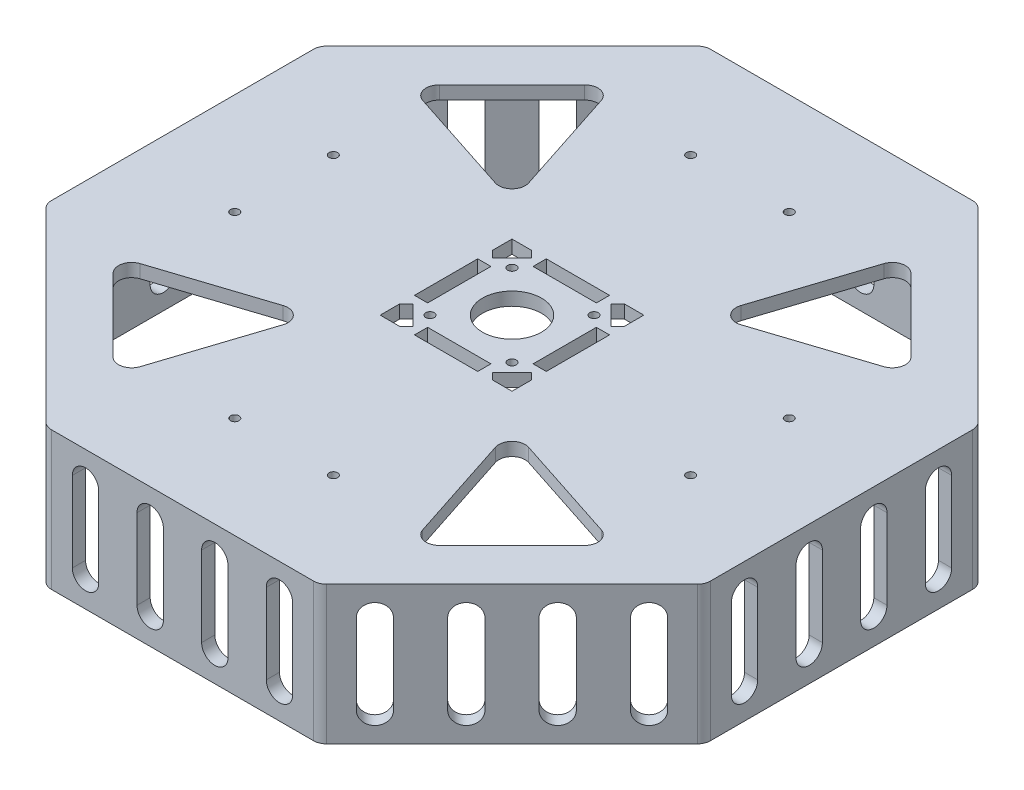
SolidWorks part; units mm, degrees
ref_plane "Front Plane" through (0, 0, 0) normal (0, 0, 1) x (1, 0, 0)
ref_plane "Top Plane" through (0, 0, 0) normal (0, 1, 0) x (1, 0, 0)
ref_plane "Right Plane" through (0, 0, 0) normal (1, 0, 0) x (0, 0, -1)
sketch "Sketch3" plane through (0, 0, 0) normal (0, 1, 0) x (1, 0, 0)
  line L0 (-95.201, 56.1198) -> (-56.1198, 95.201)
  line L7 (-51.7767, 125) -> (-125, 51.7767)
  line L8 (-125, 51.7767) -> (-125, -51.7767)
  line L9 (-125, -51.7767) -> (-51.7767, -125)
  line L10 (-51.7767, -125) -> (51.7767, -125)
  line L11 (51.7767, -125) -> (125, -51.7767)
  line L12 (125, -51.7767) -> (125, 51.7767)
  line L13 (125, 51.7767) -> (51.7767, 125)
  line L14 (51.7767, 125) -> (-51.7767, 125)
  line L15 (-56.1198, 95.201) -> (-37.207, 37.207)
  line L16 (-37.207, 37.207) -> (-95.201, 56.1198)
  line L17 (-47.6346, 115) -> (-115, 47.6346) construction
  line L18 (-115, 47.6346) -> (-115, -47.6346) construction
  line L19 (-115, -47.6346) -> (-47.6346, -115) construction
  line L20 (-47.6346, -115) -> (47.6346, -115) construction
  line L21 (47.6346, -115) -> (115, -47.6346) construction
  line L22 (115, -47.6346) -> (115, 47.6346) construction
  line L23 (115, 47.6346) -> (47.6346, 115) construction
  line L24 (47.6346, 115) -> (-47.6346, 115) construction
  line L25 (-56.1198, 95.201) -> (-61.7767, 100.8579) construction
  line L26 (-95.201, 56.1198) -> (-100.8579, 61.7767) construction
  line L27 (-56.1198, 95.201) -> (-61.7767, 100.8579) construction
  line L28 (-56.1198, 95.201) -> (-41.9777, 109.3431) construction
  line L29 (-61.7767, 100.8579) -> (-47.6346, 115) construction
  line L30 (-41.9777, 109.3431) -> (-47.6346, 115) construction
  line L31 (-95.201, 56.1198) -> (-100.8579, 61.7767) construction
  line L32 (-95.201, 56.1198) -> (-109.3431, 41.9777) construction
  line L33 (-100.8579, 61.7767) -> (-115, 47.6346) construction
  line L34 (-109.3431, 41.9777) -> (-115, 47.6346) construction
  line L35 (37.207, 37.207) -> (56.1198, 95.201)
  line L36 (56.1198, 95.201) -> (95.201, 56.1198)
  line L37 (95.201, 56.1198) -> (37.207, 37.207)
  line L38 (37.207, -37.207) -> (95.201, -56.1198)
  line L39 (95.201, -56.1198) -> (56.1198, -95.201)
  line L40 (56.1198, -95.201) -> (37.207, -37.207)
  line L41 (-37.207, -37.207) -> (-56.1198, -95.201)
  line L42 (-56.1198, -95.201) -> (-95.201, -56.1198)
  line L43 (-95.201, -56.1198) -> (-37.207, -37.207)
  line L44 (-25, -25) -> (-25, 25)
  line L45 (-20, -20) -> (20, -20) construction
  line L46 (-20, -20) -> (-20, 20) construction
  line L47 (-20, 20) -> (20, 20) construction
  line L48 (20, -20) -> (20, 20) construction
  line L49 (-20, -20) -> (20, 20) construction
  line L50 (-20, 20) -> (20, -20) construction
  line L51 (-25, 25) -> (25, 25)
  line L52 (25, -25) -> (25, 25)
  line L53 (-25, -25) -> (25, -25)
  line L54 (-25, 12) -> (-20, 12)
  line L55 (-12, -25) -> (12, -25)
  line L56 (-12, -25) -> (-12, -20)
  line L57 (-12, -20) -> (12, -20)
  line L58 (12, -25) -> (12, -20)
  line L59 (-12, -25) -> (12, -20) construction
  line L60 (-12, -20) -> (12, -25) construction
  line L61 (-25, 12) -> (-25, -12)
  line L62 (-25, -12) -> (-20, -12)
  line L63 (-20, 12) -> (-20, -12)
  line L64 (12, 25) -> (12, 20)
  line L65 (12, 25) -> (-12, 25)
  line L66 (-12, 25) -> (-12, 20)
  line L67 (12, 20) -> (-12, 20)
  line L68 (25, -12) -> (20, -12)
  line L69 (25, -12) -> (25, 12)
  line L70 (25, 12) -> (20, 12)
  line L71 (20, -12) -> (20, 12)
  line L72 (-22.5, 15.1461) -> (-15.1461, 22.5)
  line L73 (-22.5, 15.1461) -> (-25, 17.6461)
  line L74 (-15.1461, 22.5) -> (-17.6461, 25)
  line L75 (-25, 17.6461) -> (-17.6461, 25) construction
  line L76 (-22.5, 15.1461) -> (-17.6461, 25) construction
  line L77 (-15.1461, 22.5) -> (-25, 17.6461) construction
  line L78 (15.1461, 22.5) -> (22.5, 15.1461)
  line L79 (15.1461, 22.5) -> (17.6461, 25)
  line L81 (22.5, 15.1461) -> (25, 17.6461)
  line L82 (22.5, -15.1461) -> (15.1461, -22.5)
  line L83 (22.5, -15.1461) -> (25, -17.6461)
  line L85 (15.1461, -22.5) -> (17.6461, -25)
  line L86 (-15.1461, -22.5) -> (-22.5, -15.1461)
  line L87 (-15.1461, -22.5) -> (-17.6461, -25)
  line L89 (-22.5, -15.1461) -> (-25, -17.6461)
  line L90 (-17.6461, -25) -> (-25, -17.6461) [skipped]
  line L91 (17.6461, 25) -> (25, 17.6461) [skipped]
  line L92 (25, -17.6461) -> (17.6461, -25) [skipped]
  circle A0 centre (0, 0) radius 125 construction
  circle A1 centre (0, 0) radius 11.2
  circle A2 centre (-15.55, 15.55) radius 1.625
  circle A3 centre (15.55, 15.55) radius 1.625
  circle A4 centre (15.55, -15.55) radius 1.625
  circle A5 centre (-15.55, -15.55) radius 1.625
  point P38 (0, 0)
  point P43 (0, -22.5)
  point P52 (0, 0)
  point P53 (0, 20)
  point P54 (-20, 0)
  point P61 (0, -20)
  point P77 (0, 0)
  point P78 (-22.5, 12)
  point P79 (-12, 22.5)
  point P96 (0, 0)
  dimension "D1" = 250
  dimension "D7" = 11.2
  dimension "D8" = 3.25
  dimension "D2" = 10
  dimension "D3" = 20
  dimension "D4" = 8
  dimension "D5" = 61
  dimension "D10" = 31.1
  dimension "D11" = 40
  dimension "D13" = 24
  dimension "D14" = 4
  dimension "D15" = 10.4
  dimension "D16" = 4
  dimension "D12" = 5
  dimension "D6" = 4
  dimension "D9" = 4
extrude "Boss-Extrude3" add sketch "Sketch3" along normal blind 5 contours L13 L14 L7 L8 L9 L10 L11 L12 L53 L44 L51 L52 L15 L16 L0 L36 L37 L35 L39 L40 L38 L42 L43 L41 | L89 L86 L87 L53 L56 L57 L58 L85 L82 L83 L52 L68 L71 L70 L81 L78 L79 L51 L64 L67 L66 L74 L72 L73 L44 L54 L63 L62 A5 A4 A3 A2 A1 region at (0, 0, -121.4645) region at (-24.2929, 0, 14.823)
sketch "Sketch5" plane through (0, 0, 0) normal (0, -1, 0) x (1, 0, 0)
  line L16 (-51.7767, 125) -> (51.7767, 125) construction
  line L17 (51.7767, 125) -> (-51.7767, 125)
  line L18 (-51.7767, 125) -> (-125, 51.7767)
  line L19 (-125, 51.7767) -> (-125, -51.7767)
  line L20 (-125, -51.7767) -> (-51.7767, -125)
  line L21 (-51.7767, -125) -> (51.7767, -125)
  line L22 (51.7767, -125) -> (125, -51.7767)
  line L23 (125, -51.7767) -> (125, 51.7767)
  line L24 (125, 51.7767) -> (51.7767, 125)
  line L25 (125, 51.7767) -> (125, -51.7767) construction
  line L26 (-125, -51.7767) -> (-125, 51.7767) construction
  line L27 (-49.7056, 120) -> (-120, 49.7056)
  line L28 (-120, 49.7056) -> (-120, -49.7056)
  line L29 (-120, -49.7056) -> (-49.7056, -120)
  line L30 (-49.7056, -120) -> (49.7056, -120)
  line L31 (49.7056, -120) -> (120, -49.7056)
  line L32 (120, -49.7056) -> (120, 49.7056)
  line L33 (120, 49.7056) -> (49.7056, 120)
  line L34 (49.7056, 120) -> (-49.7056, 120)
  circle A0 centre (0, 0) radius 125 construction
  dimension "D1" = 5
extrude "Boss-Extrude5" add sketch "Sketch5" along normal blind 47.48
sketch "Sketch6" plane through (-88.3883, 0, 88.3883) normal (-0.7071, 0, 0.7071) x (0.7071, 0, 0.7071)
  line L0 (-51.7767, 5) -> (51.7767, 5) construction
  line L20 (-47.6346, -47.48) -> (51.7767, -47.48)
  line L22 (-47.6346, 5) -> (51.7767, 5)
  line L23 (51.7767, -47.48) -> (51.7767, 5)
  line L29 (-36.7767, -6.04) -> (-36.7767, -36.44) construction
  line L30 (-31.7767, -6.04) -> (-31.7767, -36.44)
  line L35 (-17.2589, -6.04) -> (-17.2589, -36.44)
  line L36 (51.7767, -47.48) -> (-51.7767, -47.48) construction
  line L37 (51.7767, 5) -> (51.7767, -47.48) construction
  line L43 (-41.7767, -6.04) -> (-41.7767, -36.44)
  line L44 (-51.7767, 5) -> (-51.7767, -47.48) construction
  line L45 (-7.2589, -6.04) -> (-7.2589, -36.44)
  line L46 (-12.2589, -6.04) -> (-12.2589, -36.44) construction
  line L47 (7.2589, -6.04) -> (7.2589, -36.44)
  line L48 (17.2589, -6.04) -> (17.2589, -36.44)
  line L49 (12.2589, -6.04) -> (12.2589, -36.44) construction
  line L50 (31.7767, -6.04) -> (31.7767, -36.44)
  line L51 (41.7767, -6.04) -> (41.7767, -36.44)
  line L52 (36.7767, -6.04) -> (36.7767, -36.44) construction
  arc A0 (-31.7767, -6.04) -> (-41.7767, -6.04) centre (-36.7767, -6.04) ccw
  arc A1 (-41.7767, -36.44) -> (-31.7767, -36.44) centre (-36.7767, -36.44) ccw
  arc A2 (-7.2589, -6.04) -> (-17.2589, -6.04) centre (-12.2589, -6.04) ccw
  arc A3 (-17.2589, -36.44) -> (-7.2589, -36.44) centre (-12.2589, -36.44) ccw
  arc A4 (17.2589, -6.04) -> (7.2589, -6.04) centre (12.2589, -6.04) ccw
  arc A5 (7.2589, -36.44) -> (17.2589, -36.44) centre (12.2589, -36.44) ccw
  arc A6 (41.7767, -6.04) -> (31.7767, -6.04) centre (36.7767, -6.04) ccw
  arc A7 (31.7767, -36.44) -> (41.7767, -36.44) centre (36.7767, -36.44) ccw
  point P8 (-36.7767, -21.24)
  point P22 (-12.2589, -21.24)
  point P25 (51.7767, -21.24)
  point P30 (12.2589, -21.24)
  point P37 (36.7767, -21.24)
  dimension "D1" = 5
  dimension "D2" = 30.4
  dimension "D3" = 15
  dimension "D4" = 15
extrude "Cut-Extrude1" cut sketch "Sketch6" against normal blind 5 contours L43 A1 L30 A0 | L35 A3 L45 A2 | L47 A5 L48 A4 | L50 A7 L51 A6 region at (-114.3934, -21.24, 62.3833) region at (-97.0567, -21.24, 79.72) region at (-79.72, -21.24, 97.0567) region at (-62.3833, -21.24, 114.3934)
pattern_circular "CirPattern5" count 8 over 360 about axis through (0, 5, 0) along (0, 1, 0) of "Cut-Extrude1"
fillet "Fillet2" radius 5 28 edges at (-56.1198, 2.5, 95.201) (-95.201, 2.5, 56.1198) (-37.207, 2.5, 37.207) (56.1198, 2.5, 95.201) (49.7056, -23.74, 120) (95.201, 2.5, 56.1198) (37.207, 2.5, 37.207) (37.207, 2.5, -37.207) (95.201, 2.5, -56.1198) (56.1198, 2.5, -95.201) (-95.201, 2.5, -56.1198) (-37.207, 2.5, -37.207) (-56.1198, 2.5, -95.201) (49.7056, -23.74, -120) (51.7767, -21.24, -125) (120, -23.74, 49.7056) (120, -23.74, -49.7056) (125, -21.24, -51.7767) (125, -21.24, 51.7767) (51.7767, -21.24, 125) (-51.7767, -21.24, 125) (-49.7056, -23.74, 120) (-125, -21.24, 51.7767) (-120, -23.74, 49.7056) (-49.7056, -23.74, -120) (-120, -23.74, -49.7056) (-125, -21.24, -51.7767) (-51.7767, -21.24, -125)
sketch "Sketch7" plane through (0, 5, 0) normal (0, 1, 0) x (1, 0, 0)
  line L0 (-125, 0) -> (125, 0) construction
  line L1 (-125, 49.7056) -> (-125, -49.7056) construction
  line L2 (125, -49.7056) -> (125, 49.7056) construction
  circle A2 centre (-86.475, 18.7) radius 1.625
  circle A3 centre (-86.475, -18.7) radius 1.625
  circle A4 centre (18.7, 86.475) radius 1.625
  circle A5 centre (-18.7, 86.475) radius 1.625
  circle A6 centre (86.475, -18.7) radius 1.625
  circle A7 centre (86.475, 18.7) radius 1.625
  circle A8 centre (-18.7, -86.475) radius 1.625
  circle A9 centre (18.7, -86.475) radius 1.625
  point P25 (0, 0)
  dimension "D1" = 37.4
  dimension "D2" = 3.25
  dimension "D3" = 172.95
  dimension "D4" = 4
extrude "Cut-Extrude2" cut sketch "Sketch7" against normal up to surface (5 mm away)
